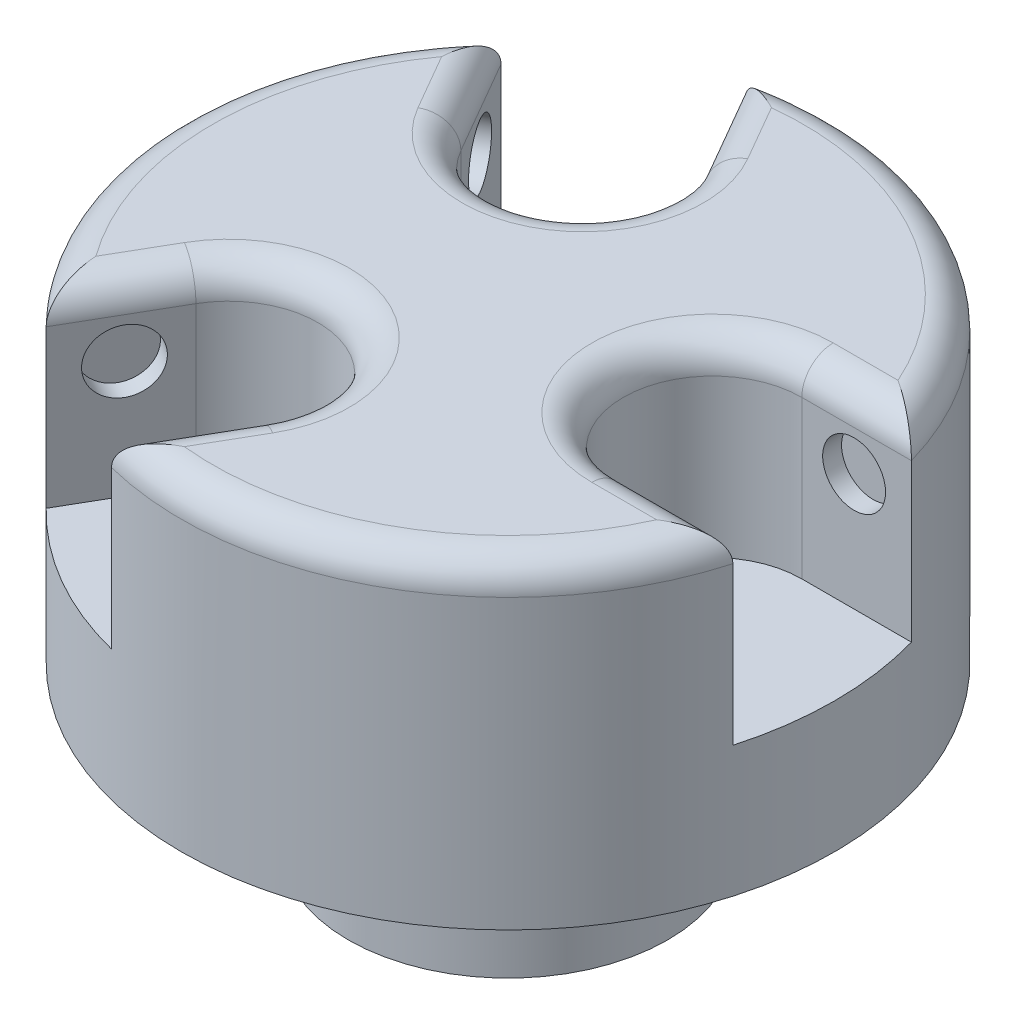
SolidWorks part; units mm, degrees
material "6061-T6 (SS)"
ref_plane "Front Plane" through (0, 0, 0) normal (0, 0, 1) x (1, 0, 0)
ref_plane "Top Plane" through (0, 0, 0) normal (0, 1, 0) x (1, 0, 0)
ref_plane "Right Plane" through (0, 0, 0) normal (1, 0, 0) x (0, 0, -1)
sketch "Sketch1" plane through (0, 0, 0) normal (0, 1, 0) x (1, 0, 0)
  circle A0 centre (0, 0) radius 51.94
  dimension "D1" = 103.88
extrude "Boss-Extrude1" add sketch "Sketch1" along normal blind 50.8
sketch "Sketch2" plane through (0, 50.8, 0) normal (0, 1, 0) x (1, 0, 0)
  line L0 (49.9616, 14.1985) -> (32.5276, 14.1985)
  line L1 (32.5276, -14.1985) -> (49.9616, -14.1985)
  circle A0 centre (0, 0) radius 51.94 construction
  arc A1 (32.5276, 14.1985) -> (32.5276, -14.1985) centre (32.5276, 0) ccw
extrude "Cut-Extrude1" cut sketch "Sketch2" against normal blind 30 and the other way through all
sketch "Sketch3" plane through (0, 0, -14.1985) normal (0, 0, 1) x (1, 0, 0)
  circle A0 centre (40.8488, 39.399) radius 5
  dimension "D1" = 10
extrude "Cut-Extrude2" cut sketch "Sketch3" against normal blind 3
mirror "Mirror1" about plane through (0, 0, 0) normal (0, 0, 1) of "Cut-Extrude2"
sketch "Sketch4" plane through (0, 50.8, 0) normal (0, 1, 0) x (1, 0, 0)
  point P0 (0, 0)
ref_axis "Axis1" through (0, 50.8, 0) along (0, -1, 0)
pattern_circular "CirPattern1" count 3 over 360 about axis through (0, 50.8, 0) along (0, -1, 0) of "Cut-Extrude1", "Cut-Extrude2", "Mirror1"
fillet "Fillet2" radius 5 12 edges at (41.2446, 50.8, -14.1985) (18.3291, 50.8, 0) (41.2446, 50.8, 14.1985) (25.97, 50.8, 44.9814) (-8.326, 50.8, 42.8181) (-9.1645, 50.8, 15.8735) (-32.9186, 50.8, 28.6196) (-51.94, 50.8, 0) (-32.9186, 50.8, -28.6196) (-9.1645, 50.8, -15.8735) (-8.326, 50.8, -42.8181) (25.97, 50.8, -44.9814)
sketch "Sketch6" plane through (0, 0, 0) normal (0, -1, 0) x (1, 0, 0)
  circle A0 centre (0, 0) radius 25.4
  dimension "D1" = 50.8
extrude "Boss-Extrude2" add sketch "Sketch6" along normal blind 25.4
